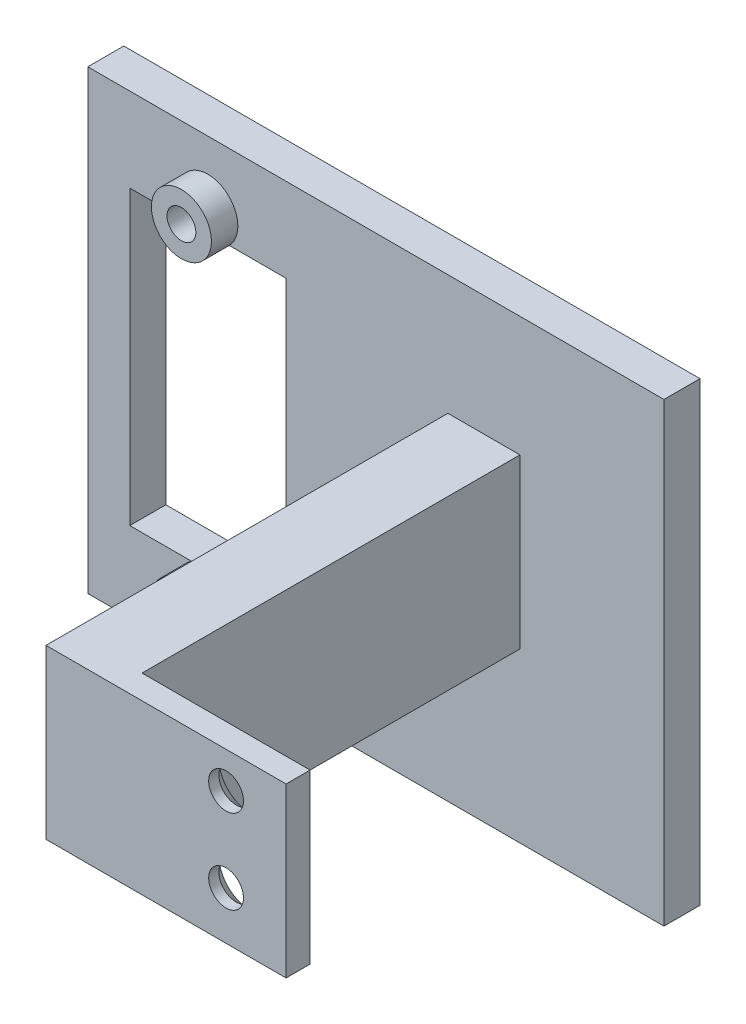
SolidWorks part; units mm, degrees
ref_plane "Front Plane" through (0, 0, 0) normal (0, 0, 1) x (1, 0, 0)
ref_plane "Top Plane" through (0, 0, 0) normal (0, 1, 0) x (1, 0, 0)
ref_plane "Right Plane" through (0, 0, 0) normal (1, 0, 0) x (0, 0, -1)
sketch "Sketch1" plane through (0, 0, 0) normal (0, 0, 1) x (1, 0, 0)
  line L1 (-70, 0) -> (-22, 0)
  line L2 (-70, 0) -> (-70, 38)
  line L3 (-70, 38) -> (-22, 38)
  line L4 (-22, 0) -> (-22, 38)
  line L6 (-66.5, 6.65) -> (-53.5, 6.65)
  line L7 (-66.5, 6.65) -> (-66.5, 31)
  line L8 (-66.5, 31) -> (-53.5, 31)
  line L9 (-53.5, 6.65) -> (-53.5, 31)
extrude "Servo_Shelf" add sketch "Sketch1" along normal blind 3 from offset 36.48 offset against normal yes
sketch "Sketch2" plane through (0, 0, 0) normal (0, 0, 1) x (1, 0, 0)
  line L1 (-40, 14) -> (-34, 14)
  line L2 (-40, 14) -> (-40, 28)
  line L3 (-40, 28) -> (-34, 28)
  line L4 (-34, 14) -> (-34, 28)
extrude "Outboard_Riser" add sketch "Sketch2" along normal blind 33.48 from offset 34.48 offset against normal yes
sketch "Sketch3" plane through (0, 0, 0) normal (0, 0, 1) x (1, 0, 0)
  line L1 (-40, 14) -> (-20, 14)
  line L2 (-40, 14) -> (-40, 28)
  line L3 (-40, 28) -> (-20, 28)
  line L4 (-20, 14) -> (-20, 28)
extrude "Plate_Attachment_Foot" add sketch "Sketch3" along normal blind 2 from offset 2 offset against normal yes
sketch "Sketch4" plane through (0, 0, -2) normal (0, 0, -1) x (-1, 0, 0)
  circle A0 centre (25, 18) radius 1.45
  circle A1 centre (25, 25) radius 1.45
extrude "Servo_Pad_D2p9" cut sketch "Sketch4" against normal blind 2.01
sketch "Sketch5" plane through (0, 0, -2) normal (0, 0, -1) x (-1, 0, 0)
  circle A0 centre (25, 18) radius 2.6
  circle A1 centre (25, 25) radius 2.6
extrude "Servo_Pad_CSK_D5p2_90deg" cut sketch "Sketch5" against normal blind 1.15 draft 45
sketch "Sketch6" plane through (0, 0, 0) normal (0, 0, 1) x (1, 0, 0)
  circle A0 centre (-60, 4.55) radius 2.5
  circle A1 centre (-60, 32.75) radius 2.5
extrude "Servo_Ear_Supports_H2p2" add sketch "Sketch6" along normal blind 2.2 from offset 33.48 offset against normal yes
sketch "Sketch7" plane through (0, 0, -31.28) normal (0, 0, 1) x (1, 0, 0)
  circle A0 centre (-60, 4.55) radius 1.2
  circle A1 centre (-60, 32.75) radius 1.2
extrude "Servo_Ear_D2p4_Through" cut sketch "Sketch7" against normal blind 5.21
